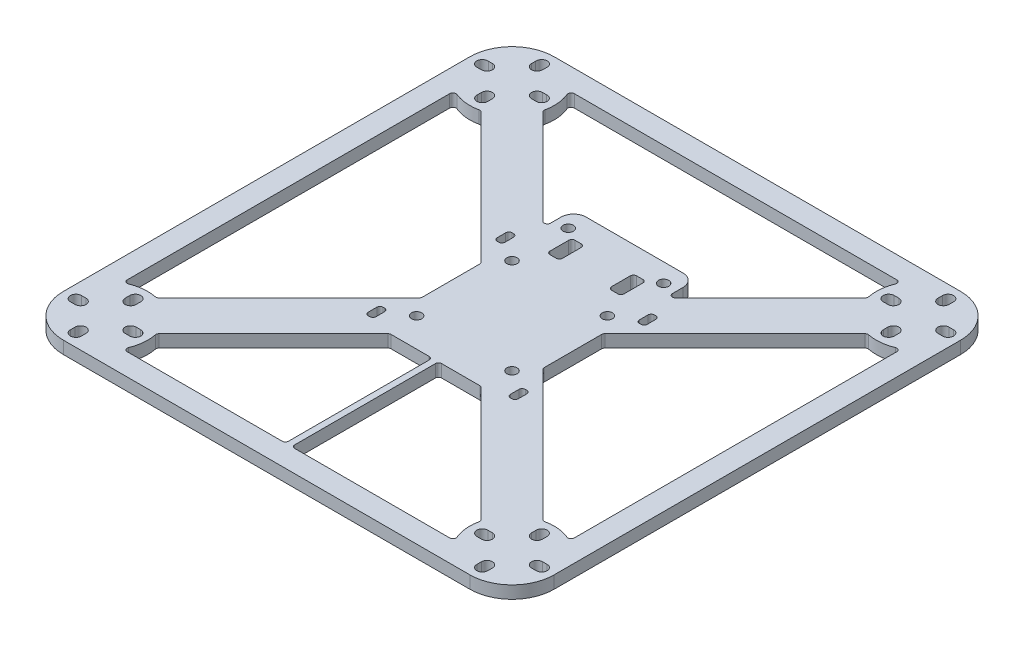
SolidWorks part; units mm, degrees
ref_plane "Front Plane" through (0, 0, 0) normal (0, 0, 1) x (1, 0, 0)
ref_plane "Top Plane" through (0, 0, 0) normal (0, 1, 0) x (1, 0, 0)
ref_plane "Right Plane" through (0, 0, 0) normal (1, 0, 0) x (0, 0, -1)
sketch "Sketch1" plane through (0, 0, 0) normal (0, 1, 0) x (1, 0, 0)
  line L0 (0, 78.5) -> (0, -78.5) construction
  line L1 (-78.5, 78.5) -> (78.5, 78.5)
  line L2 (-78.5, 78.5) -> (-78.5, -78.5)
  line L3 (-78.5, -78.5) -> (78.5, -78.5)
  line L4 (78.5, 78.5) -> (78.5, -78.5)
  line L5 (-78.5, 78.5) -> (78.5, -78.5) construction
  line L6 (-78.5, -78.5) -> (78.5, 78.5) construction
  line L7 (78.5, 0) -> (-78.5, 0) construction
  line L8 (-1, 65) -> (-1, 0) construction
  line L9 (-83.4497, 73.5503) -> (73.5503, -83.4497)
  line L10 (-73.5503, 83.4497) -> (83.4497, -73.5503)
  line L11 (-73.5503, -83.4497) -> (83.4497, 73.5503)
  line L12 (-83.4497, -73.5503) -> (73.5503, 83.4497)
  line L13 (-53.1678, 71.5) -> (53.1678, 71.5)
  line L14 (-53.1678, -71.5) -> (53.1678, -71.5)
  line L15 (71.5, -53.1678) -> (71.5, 53.1678)
  line L16 (-71.5, -53.1678) -> (-71.5, 53.1678)
  circle A0 centre (-65, 65) radius 13.5
  circle A1 centre (-65, 65) radius 64
  circle A2 centre (65, 65) radius 13.5
  circle A3 centre (-65, -65) radius 13.5
  circle A4 centre (65, -65) radius 13.5
  point P0 (0, 0)
  dimension "D1" = 27
  dimension "D2" = 128
  dimension "D3" = 2
  dimension "D4" = 14
  dimension "D5" = 7
extrude "Base shape" add sketch "Sketch1" along normal blind 4 contours L12 A3 L11 L9 | A4 L10 L11 L9 | L11 A2 L12 L10 | L9 A1 L10 A0 | A1 L9 L12 L10 | L12 L9 L11 L10 | L13 A1 L1 A0 | L13 A2 L1 A1 | A4 L4 A2 L15 | A4 L14 A3 L3 | L2 A3 L16 A1 | L2 A1 L16 A0 | A0 | A2 | A4 | A3 region at (-29.268, 0, -75.0845) region at (-75.0845, 0, -29.268) region at (27.4447, 0, -75.1014) region at (-37.8705, 0, -37.8705) region at (-75.1014, 0, 27.4447) region at (-12.3929, 0, -12.3929) region at (30.427, 0, -30.427) region at (0, 0, 0) region at (-30.427, 0, 30.427) region at (30.427, 0, 30.427) region at (75.0932, 0, 0) region at (0, 0, 75.0932)
sketch "Sketch2" plane through (0, 4, 0) normal (0, 1, 0) x (1, 0, 0)
  line L0 (-65, 74.5) -> (-65, 55.5) construction
  line L1 (-74.5, 65) -> (-55.5, 65) construction
  line L2 (0, 78.5) -> (0, -78.5) construction
  line L3 (-65, 78.5) -> (65, 78.5) construction
  line L4 (-65, -78.5) -> (65, -78.5) construction
  line L5 (-78.5, 0) -> (78.5, 0) construction
  line L6 (-78.5, 65) -> (-78.5, -65) construction
  line L7 (78.5, 65) -> (78.5, -65) construction
  line L8 (-66.75, 74.5) -> (-66.75, 73)
  line L9 (-63.25, 74.5) -> (-63.25, 73)
  line L10 (-74.5, 66.75) -> (-73, 66.75)
  line L11 (-74.5, 63.25) -> (-73, 63.25)
  line L12 (-66.75, 57) -> (-66.75, 55.5)
  line L13 (-63.25, 57) -> (-63.25, 55.5)
  line L14 (-57, 66.75) -> (-55.5, 66.75)
  line L15 (-57, 63.25) -> (-55.5, 63.25)
  line L16 (63.25, 57) -> (63.25, 55.5)
  line L17 (66.75, 57) -> (66.75, 55.5)
  line L18 (74.5, 63.25) -> (73, 63.25)
  line L19 (74.5, 66.75) -> (73, 66.75)
  line L20 (63.25, 74.5) -> (63.25, 73)
  line L21 (66.75, 74.5) -> (66.75, 73)
  line L22 (57, 66.75) -> (55.5, 66.75)
  line L23 (57, 63.25) -> (55.5, 63.25)
  line L24 (-66.75, -57) -> (-66.75, -55.5)
  line L25 (-63.25, -57) -> (-63.25, -55.5)
  line L26 (-57, -63.25) -> (-55.5, -63.25)
  line L27 (-57, -66.75) -> (-55.5, -66.75)
  line L28 (-74.5, -63.25) -> (-73, -63.25)
  line L29 (-74.5, -66.75) -> (-73, -66.75)
  line L30 (-63.25, -74.5) -> (-63.25, -73)
  line L31 (-66.75, -74.5) -> (-66.75, -73)
  line L32 (57, -63.25) -> (55.5, -63.25)
  line L33 (57, -66.75) -> (55.5, -66.75)
  line L34 (66.75, -74.5) -> (66.75, -73)
  line L35 (63.25, -74.5) -> (63.25, -73)
  line L36 (74.5, -66.75) -> (73, -66.75)
  line L37 (74.5, -63.25) -> (73, -63.25)
  line L38 (66.75, -57) -> (66.75, -55.5)
  line L39 (63.25, -57) -> (63.25, -55.5)
  circle A0 centre (-65, 65) radius 9.5
  circle A1 centre (-65, 65) radius 8
  circle A2 centre (-65, 74.5) radius 1.75
  circle A3 centre (-65, 55.5) radius 1.75
  circle A4 centre (-57, 65) radius 1.75
  circle A5 centre (-73, 65) radius 1.75
  circle A6 centre (-65, 73) radius 1.75
  circle A7 centre (-55.5, 65) radius 1.75
  circle A8 centre (-74.5, 65) radius 1.75
  circle A9 centre (-65, 57) radius 1.75
  circle A10 centre (65, 57) radius 1.75
  circle A11 centre (65, 55.5) radius 1.75
  circle A12 centre (73, 65) radius 1.75
  circle A13 centre (74.5, 65) radius 1.75
  circle A14 centre (65, 73) radius 1.75
  circle A15 centre (65, 74.5) radius 1.75
  circle A16 centre (57, 65) radius 1.75
  circle A17 centre (55.5, 65) radius 1.75
  circle A18 centre (-65, -57) radius 1.75
  circle A19 centre (-65, -55.5) radius 1.75
  circle A20 centre (-57, -65) radius 1.75
  circle A21 centre (-55.5, -65) radius 1.75
  circle A22 centre (-74.5, -65) radius 1.75
  circle A23 centre (-73, -65) radius 1.75
  circle A24 centre (-65, -74.5) radius 1.75
  circle A25 centre (-65, -73) radius 1.75
  circle A26 centre (55.5, -65) radius 1.75
  circle A27 centre (57, -65) radius 1.75
  circle A28 centre (65, -74.5) radius 1.75
  circle A29 centre (65, -73) radius 1.75
  circle A30 centre (74.5, -65) radius 1.75
  circle A31 centre (73, -65) radius 1.75
  circle A32 centre (65, -55.5) radius 1.75
  circle A33 centre (65, -57) radius 1.75
  dimension "D1" = 19
  dimension "D2" = 16
  dimension "D3" = 3.5
extrude "Motor mounting holes" cut sketch "Sketch2" against normal up to next contours A27 A26 | A26 A27 | A27 A26 | A27 L32 A26 | A27 A26 L33 | A29 A28 | A28 A29 | A28 A29 | A29 L35 A28 | A29 A28 L34 | A31 A30 | A30 A31 | A31 A30 | A31 A30 L37 | A31 L36 A30 | A33 A32 | A32 A33 | A33 A32 | A33 A32 L39 | A33 L38 A32 | A17 A16 | A17 A16 | A16 A17 | L22 A17 A16 | A16 A17 L23 | A11 A10 | A11 A10 | A10 A11 | L16 A11 A10 | A10 A11 L17 | A12 A13 | A13 A12 | A13 A12 | A12 A13 L19 | L18 A13 A12 | A14 A15 | A15 A14 | A15 A14 | A14 A15 L20 | L21 A15 A14 | A8 A5 L10 A0 | A8 A0 L11 A5 | A6 A2 A0 L8 | A6 L9 A0 A2 | A7 A4 L15 A0 | A7 A0 L14 A4 | A9 L12 A0 A3 | A9 A3 A0 L13 | A19 A18 | A19 A18 | A18 A19 | A18 A19 L24 | L25 A19 A18 | A22 A23 | A23 A22 | A23 A22 | A22 A23 L28 | L29 A23 A22 | A21 A20 | A21 A20 | A20 A21 | A20 A21 L26 | L27 A21 A20 | A24 A25 | A25 A24 | A25 A24 | A24 A25 L31 | L30 A25 A24 | A8 | A5 | A2 | A6 | A4 | A7 | A9 | A3 region at (-66.6996, 4, -73.7469) region at (-73.7469, 4, -66.6996) region at (-63.3004, 4, -73.7469) region at (-56.2531, 4, -66.6996) region at (-73.7469, 4, -63.3004) region at (-66.6996, 4, -56.2531) region at (-56.2531, 4, -63.3004) region at (-63.3004, 4, -56.2531) region at (63.3002, 4, -56.25) region at (65, 4, -57.6692) region at (65, 4, -54.8308) region at (66.6998, 4, -56.25) region at (65, 4, -56.25) region at (75.1692, 4, -65) region at (73.75, 4, -63.3002) region at (72.3308, 4, -65) region at (73.75, 4, -65) region at (73.75, 4, -66.6998) region at (63.3002, 4, -73.75) region at (65, 4, -75.1692) region at (65, 4, -72.3308) region at (66.6998, 4, -73.75) region at (65, 4, -73.75) region at (56.25, 4, -66.6998) region at (57.6692, 4, -65) region at (54.8308, 4, -65) region at (56.25, 4, -65) region at (56.25, 4, -63.3002) region at (-65, 4, 57.6692) region at (-66.6998, 4, 56.25) region at (-65, 4, 54.8308) region at (-63.3002, 4, 56.25) region at (-65, 4, 56.25) region at (-57.6692, 4, 65) region at (-56.25, 4, 63.3002) region at (-54.8308, 4, 65) region at (-56.25, 4, 66.6998) region at (-56.25, 4, 65) region at (-75.1692, 4, 65) region at (-73.75, 4, 63.3002) region at (-72.3308, 4, 65) region at (-73.75, 4, 66.6998) region at (-73.75, 4, 65) region at (-63.3002, 4, 73.75) region at (-65, 4, 75.1692) region at (-65, 4, 72.3308) region at (-66.6998, 4, 73.75) region at (-65, 4, 73.75) region at (56.25, 4, 63.3002) region at (57.6692, 4, 65) region at (54.8308, 4, 65) region at (56.25, 4, 65) region at (56.25, 4, 66.6998) region at (66.6998, 4, 73.75) region at (65, 4, 75.1692) region at (65, 4, 72.3308) region at (63.3002, 4, 73.75) region at (65, 4, 73.75) region at (75.1692, 4, 65) region at (73.75, 4, 66.6998)
sketch "Sketch5" plane through (0, 0, 0) normal (0, -1, 0) x (1, 0, 0)
  line L3 (-19.5, 10.25) -> (19.5, 10.25)
  line L4 (-19.5, 10.25) -> (-19.5, -10.25)
  line L7 (-19.5, -10.25) -> (19.5, -10.25)
  line L8 (19.5, 10.25) -> (19.5, -10.25)
  line L16 (-15.5, -39.2) -> (15.5, -39.2)
  line L17 (19.5, -35.2) -> (19.5, -10.25)
  line L18 (19.5, -10.25) -> (17.5, -10.25)
  line L19 (17.5, -10.25) -> (17.5, 10.25)
  line L20 (17.5, 10.25) -> (19.5, 10.25)
  line L21 (19.5, 10.25) -> (19.5, 24.5)
  line L22 (19.5, 24.5) -> (-19.5, 24.5)
  line L23 (-19.5, 24.5) -> (-19.5, 10.25)
  line L24 (-19.5, 10.25) -> (-17.5, 10.25)
  line L25 (-17.5, 10.25) -> (-17.5, -10.25)
  line L26 (-17.5, -10.25) -> (-19.5, -10.25)
  line L27 (-19.5, -10.25) -> (-19.5, -35.2)
  line L28 (-15.5, -39.2) -> (15.5, -39.2)
  line L29 (19.5, -35.2) -> (19.5, -10.25)
  line L30 (19.5, -10.25) -> (17.5, -10.25)
  line L31 (17.5, -10.25) -> (17.5, 10.25)
  line L32 (17.5, 10.25) -> (19.5, 10.25)
  line L33 (19.5, 10.25) -> (19.5, 24.5)
  line L34 (19.5, 24.5) -> (-19.5, 24.5)
  line L35 (-19.5, 24.5) -> (-19.5, 10.25)
  line L36 (-19.5, 10.25) -> (-17.5, 10.25)
  line L37 (-17.5, 10.25) -> (-17.5, -10.25)
  line L38 (-17.5, -10.25) -> (-19.5, -10.25)
  line L39 (-19.5, -10.25) -> (-19.5, -35.2)
  arc A2 (15.5, -39.2) -> (19.5, -35.2) centre (15.5, -35.2) ccw
  arc A3 (-19.5, -35.2) -> (-15.5, -39.2) centre (-15.5, -35.2) ccw
  arc A4 (15.5, -39.2) -> (19.5, -35.2) centre (15.5, -35.2) ccw
  arc A5 (-19.5, -35.2) -> (-15.5, -39.2) centre (-15.5, -35.2) ccw
  dimension "D1" = 0
extrude "OSD cover" add sketch "Sketch5" against normal up to surface (4 mm away) contours L34 L35 L3 L33 | L3 L37 L7 L31 | L37 L3 L4 L7 | L31 L7 L8 L3 | L39 A5 L28 A4 L29 L7 region at (0, 0, 17.375) region at (-18.5, 0, 0) region at (0, 0, 0) region at (0, 0, -24.6419) region at (18.5, 0, 0) up to face at (65, 4, 73.75)
sketch "Sketch7" plane through (0, 4, 0) normal (0, 1, 0) x (1, 0, 0)
  line L0 (18, 23) -> (-18, 23) construction
  line L1 (-8.85, 23) -> (-10.85, 23)
  line L2 (-7.85, 24) -> (-7.85, 30)
  line L3 (-8.85, 31) -> (-10.85, 31)
  line L4 (-11.85, 24) -> (-11.85, 30)
  line L5 (-7.85, 39.2) -> (-7.85, 23) construction
  line L6 (0, -24.5) -> (0, 39.2) construction
  line L10 (7.85, 39.2) -> (-4.95, 39.2) construction
  line L11 (8.85, 31) -> (10.85, 31)
  line L12 (11.85, 24) -> (11.85, 30)
  line L13 (8.85, 23) -> (10.85, 23)
  line L14 (7.85, 24) -> (7.85, 30)
  line L15 (14.6005, -24.5) -> (-14.6005, -24.5) construction
  circle A0 centre (-15.25, -15.25) radius 1.65 construction
  circle A1 centre (-15.25, 15.25) radius 1.65 construction
  circle A2 centre (-15.25, 33.25) radius 1.65 construction
  circle A3 centre (15.25, 33.25) radius 1.65 construction
  circle A4 centre (15.25, 15.25) radius 1.65 construction
  circle A5 centre (15.25, -15.25) radius 1.65 construction
  circle A6 centre (-15.25, -15.25) radius 1.65
  circle A7 centre (-15.25, 15.25) radius 1.65
  circle A8 centre (-15.25, 33.25) radius 1.65
  circle A9 centre (15.25, 33.25) radius 1.65
  circle A10 centre (15.25, 15.25) radius 1.65
  circle A11 centre (15.25, -15.25) radius 1.65
  arc A12 (8.85, 23) -> (7.85, 24) centre (8.85, 24) cw
  arc A13 (11.85, 24) -> (10.85, 23) centre (10.85, 24) cw
  arc A14 (10.85, 31) -> (11.85, 30) centre (10.85, 30) cw
  arc A15 (8.85, 31) -> (7.85, 30) centre (8.85, 30) ccw
  arc A16 (-10.85, 23) -> (-11.85, 24) centre (-10.85, 24) cw
  arc A17 (-8.85, 23) -> (-7.85, 24) centre (-8.85, 24) ccw
  arc A18 (-7.85, 30) -> (-8.85, 31) centre (-8.85, 30) ccw
  arc A19 (-10.85, 31) -> (-11.85, 30) centre (-10.85, 30) ccw
  point P29 (0, 0)
  point P40 (7.85, 23)
  point P43 (11.85, 23)
  point P46 (11.85, 31)
  point P49 (7.85, 31)
  point P52 (-11.85, 23)
  point P55 (-7.85, 23)
  point P58 (-7.85, 31)
  point P61 (-11.85, 31)
  dimension "D2" = 8
  dimension "D3" = 1
  dimension "D1" = 4
extrude "Main holes" cut sketch "Sketch7" against normal up to next contours A11 | A10 | A9 | A8 | A7 | A6 | L3 A19 L4 A16 L1 A17 L2 A18 | L11 A14 L12 A13 L13 A12 L14 A15
sketch "Sketch8" plane through (0, 0, 0) normal (0, -1, 0) x (1, 0, 0)
  line L0 (0, 78.5) -> (0, -71.5) construction
  line L1 (-65, 78.5) -> (65, 78.5) construction
  line L2 (-53.1678, -71.5) -> (53.1678, -71.5) construction
  line L4 (-1, 24.5) -> (1, 24.5)
  line L5 (-1, 24.5) -> (-1, 71.5)
  line L6 (-1, 71.5) -> (1, 71.5)
  line L7 (1, 24.5) -> (1, 71.5)
  line L8 (-53.1678, 71.5) -> (53.1678, 71.5) construction
  line L9 (0, 71.5) -> (0, 24.5) construction
  line L10 (-19.5, 24.5) -> (19.5, 24.5) construction
  point P10 (-1, 25.576)
  point P16 (0, 0)
  dimension "D1" = 2
extrude "VTX wire support" add sketch "Sketch8" against normal up to surface (4 mm away) up to face at (9.85, 4, -27)
sketch "Sketch9" plane through (0, 0, 0) normal (0, -1, 0) x (1, 0, 0)
  line L1 (22.5, 23) -> (23, 23)
  line L2 (21.5, 22) -> (21.5, 19.25)
  line L3 (22.5, 18.25) -> (23, 18.25)
  line L4 (24, 22) -> (24, 19.25)
  line L5 (0, 78.5) -> (0, -71.5) construction
  line L6 (-65, 78.5) -> (65, 78.5) construction
  line L7 (-53.1678, -71.5) -> (53.1678, -71.5) construction
  line L8 (78.5, 0) -> (-78.5, 0) construction
  line L9 (78.5, -65) -> (78.5, 65) construction
  line L10 (-78.5, -65) -> (-78.5, 65) construction
  line L11 (-24, 22) -> (-24, 19.25)
  line L12 (-22.5, 23) -> (-23, 23)
  line L13 (-21.5, 22) -> (-21.5, 19.25)
  line L14 (-22.5, 18.25) -> (-23, 18.25)
  line L15 (24, -22) -> (24, -19.25)
  line L16 (22.5, -23) -> (23, -23)
  line L17 (21.5, -22) -> (21.5, -19.25)
  line L18 (22.5, -18.25) -> (23, -18.25)
  line L19 (-21.5, -22) -> (-21.5, -19.25)
  line L20 (-22.5, -23) -> (-23, -23)
  line L21 (-24, -22) -> (-24, -19.25)
  line L22 (-22.5, -18.25) -> (-23, -18.25)
  line L25 (19.5, 24.5) -> (19.5, -35.2) construction
  arc A0 (23, 18.25) -> (24, 19.25) centre (23, 19.25) ccw
  arc A1 (21.5, 19.25) -> (22.5, 18.25) centre (22.5, 19.25) ccw
  arc A2 (22.5, 23) -> (21.5, 22) centre (22.5, 22) ccw
  arc A3 (23, 23) -> (24, 22) centre (23, 22) cw
  arc A4 (-23, 23) -> (-24, 22) centre (-23, 22) ccw
  arc A5 (-22.5, 23) -> (-21.5, 22) centre (-22.5, 22) cw
  arc A6 (-21.5, 19.25) -> (-22.5, 18.25) centre (-22.5, 19.25) cw
  arc A7 (-23, 18.25) -> (-24, 19.25) centre (-23, 19.25) cw
  arc A8 (23, -23) -> (24, -22) centre (23, -22) ccw
  arc A9 (22.5, -23) -> (21.5, -22) centre (22.5, -22) cw
  arc A10 (21.5, -19.25) -> (22.5, -18.25) centre (22.5, -19.25) cw
  arc A11 (23, -18.25) -> (24, -19.25) centre (23, -19.25) cw
  arc A12 (-22.5, -23) -> (-21.5, -22) centre (-22.5, -22) ccw
  arc A13 (-23, -23) -> (-24, -22) centre (-23, -22) cw
  arc A14 (-23, -18.25) -> (-24, -19.25) centre (-23, -19.25) ccw
  arc A15 (-21.5, -19.25) -> (-22.5, -18.25) centre (-22.5, -19.25) ccw
  point P15 (21.5, 23)
  point P18 (24, 23)
  point P69 (0, 0)
  dimension "D3" = 1
  dimension "D1" = 2
  dimension "D2" = 2.5
extrude "ESC power wire cuts" cut sketch "Sketch9" against normal up to next
fillet "Milling fillets" radius 1 28 edges at (53.1678, 2, -71.5) (51.8878, 2, -61.7873) (-53.1678, 2, -71.5) (-51.8878, 2, -61.7873) (-61.7873, 2, -51.8878) (-71.5, 2, -53.1678) (-71.5, 2, 53.1678) (-61.7873, 2, 51.8878) (-51.8878, 2, 61.7873) (-53.1678, 2, 71.5) (-1, 2, 71.5) (1, 2, 71.5) (51.8878, 2, 61.7873) (53.1678, 2, 71.5) (61.7873, 2, -51.8878) (71.5, 2, -53.1678) (61.7873, 2, 51.8878) (71.5, 2, 53.1678) (19.5, 2, -29.3995) (-19.5, 2, -29.3995) (-19.5, 2, 9.6005) (-19.5, 2, -9.6005) (19.5, 2, -9.6005) (19.5, 2, 9.6005) (1, 2, 24.5) (-14.6005, 2, 24.5) (-1, 2, 24.5) (14.6005, 2, 24.5)
sketch "Sketch3" plane through (0, 0, 0) normal (0, -1, 0) x (1, 0, 0)
  line L0 (0, -71.5) -> (0, -83.5) construction
  line L1 (-51.5836, -71.5) -> (51.5836, -71.5) construction
  line L2 (-65, -78.5) -> (65, -78.5) construction
  line L3 (0, -83.5) -> (-5, -78.5)
  line L4 (-5, -78.5) -> (5, -78.5)
  line L5 (0, -83.5) -> (5, -78.5)
  point P10 (0, -78.5)
  dimension "D1" = 5
  dimension "D2" = 45
extrude "Forward arrow" [suppressed] add sketch "Sketch3" against normal up to surface (4 mm away) contours L4 L0 L5 | L0 L4 L3 up to face at (-22.75, 4, 20.625)
equation "\"MotorDiameter\"=27"
equation "\"D1@Sketch1\"=\"MotorDiameter\""
equation "\"PropDiameter\"=128"
equation "\"D2@Sketch1\"=\"PropDiameter\""
equation "\"PropDistance\"=2"
equation "\"D3@Sketch1\"=\"PropDistance\""
equation "\"ArmWidth\"=14"
equation "\"D4@Sketch1\"=\"ArmWidth\""
equation "\"FrameDepth\"=4"
equation "\"D1@Base shape\" = \"FrameDepth\""
equation "\"D5@Sketch1\"=\"ArmWidth\"/2"
equation "\"MotorHoleOuterDiameter\"=19"
equation "\"D1@Sketch2\"=\"MotorHoleOuterDiameter\""
equation "\"MotorHoleInnerDiameter\"=16"
equation "\"D2@Sketch2\"=\"MotorHoleInnerDiameter\""
equation "\"MotorHoleDiameter\"=3.5"
equation "\"D3@Sketch2\"=\"MotorHoleDiameter\""
